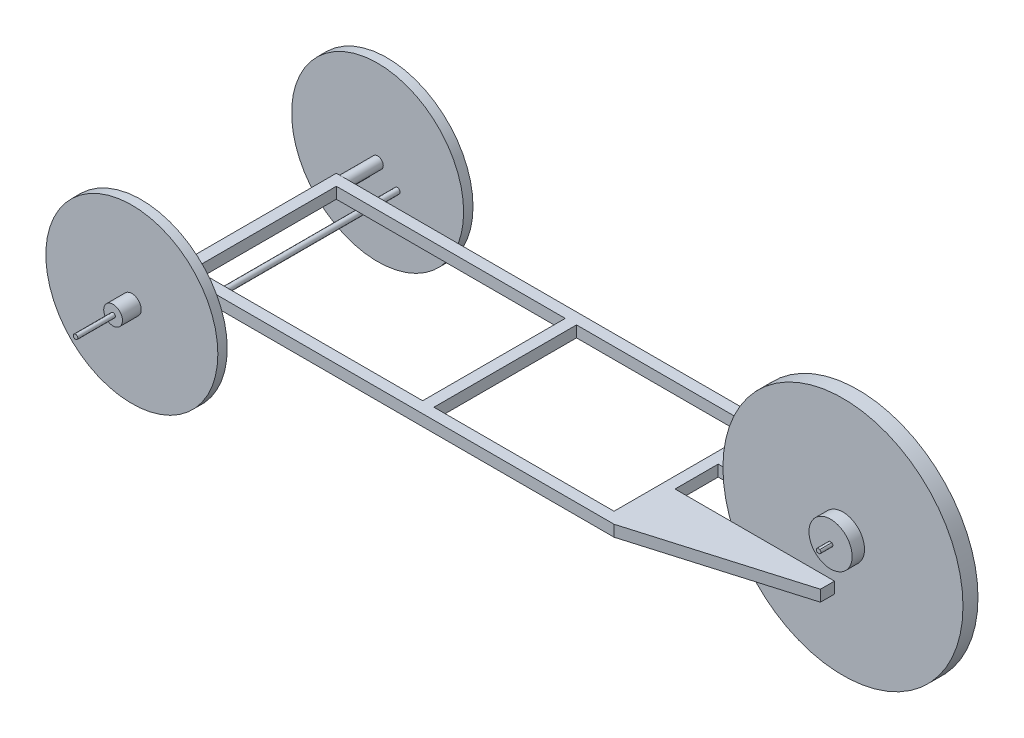
SolidWorks part; units mm, degrees
ref_plane "Front Plane" through (0, 0, 0) normal (0, 0, 1) x (1, 0, 0)
ref_plane "Top Plane" through (0, 0, 0) normal (0, 1, 0) x (1, 0, 0)
ref_plane "Right Plane" through (0, 0, 0) normal (1, 0, 0) x (0, 0, -1)
sketch "Sketch2" plane through (0, 0, 0) normal (0, 1, 0) x (1, 0, 0)
  line L0 (-560, 190) -> (-560, -190)
  line L4 (-560, 190) -> (560, 190)
  line L5 (560, 190) -> (560, -190)
  line L6 (560, -190) -> (-560, -190)
  line L8 (80, 190) -> (80, -190)
  line L9 (50, -190) -> (50, 190)
  line L10 (-560, -190) -> (560, 190) construction
  line L11 (-590, 220) -> (590, 220)
  line L12 (-590, 220) -> (-590, -220)
  line L13 (-590, -220) -> (590, -220)
  line L14 (590, 220) -> (590, -220)
  line L15 (-590, 220) -> (590, -220) construction
  line L16 (-590, 0) -> (-560, 0) construction
  line L17 (50, 0) -> (80, 0) construction
  dimension "D1" = 30
  dimension "D2" = 30
  dimension "D3" = 440
  dimension "D4" = 1180
  dimension "D5" = 540
extrude "Boss-Extrude1" add sketch "Sketch2" along normal blind 15 and the other way blind 15 contours L14 L11 L12 L13 L5 L6 L0 L4 | L9 L6 L8 L4 region at (65, 0, 0) region at (0, 0, -207.4064)
sketch "Sketch3" plane through (0, 0, 0) normal (0, 0, 1) x (1, 0, 0)
  line L0 (-590, -15) -> (590, -15) construction
  line L1 (-590, -15) -> (-590, 15) construction
  line L2 (-590, 15) -> (590, 15) construction
  circle A0 centre (-575, 0) radius 15
extrude "Boss-Extrude2" add sketch "Sketch3" along normal blind 315 and the other way blind 315
sketch "Sketch4" plane through (0, 0, 315) normal (0, 0, 1) x (1, 0, 0)
  circle A0 centre (-575, 0) radius 229.2
  dimension "D1" = 458.4
extrude "Boss-Extrude3" add sketch "Sketch4" along normal blind 25
mirror "Mirror1" about plane through (0, 0, 0) normal (0, 0, 1) of "Boss-Extrude3"
sketch "Sketch5" plane through (0, 0, 0) normal (0, 0, 1) x (1, 0, 0)
  line L0 (1000, 90.7) -> (-590, 0) construction
  line L1 (-590, -15) -> (-590, 0) construction
  line L2 (-575, -229.2) -> (1000, -229.2) construction
  line L3 (-575, 0) -> (-575, -229.2) construction
  circle A0 centre (1000, 90.7) radius 319.9
  circle A1 centre (-575, 0) radius 15 construction
  circle A2 centre (-575, 0) radius 229.2 construction
  dimension "D2" = 639.8
  dimension "D1" = 1590
extrude "Boss-Extrude4" add sketch "Sketch5" along normal blind 20 and the other way blind 20 separate body
sketch "Sketch6" plane through (0, 0, 0) normal (0, 0, 1) x (1, 0, 0)
  circle A0 centre (1000, 90.7) radius 57.5
  dimension "D1" = 115
extrude "Boss-Extrude5" add sketch "Sketch6" along normal blind 53 and the other way blind 43
sketch "Sketch7" plane through (0, 0, 0) normal (0, 0, 1) x (1, 0, 0)
  line L0 (996.6834, 95.7) -> (1003.3166, 95.7)
  line L1 (996.6834, 85.7) -> (1003.3166, 85.7)
  line L2 (1000, 85.7) -> (1000, 95.7) construction
  circle A0 centre (1000, 90.7) radius 6
  dimension "D2" = 12
  dimension "D1" = 10
extrude "Boss-Extrude6" add sketch "Sketch7" along normal blind 85 and the other way blind 75 contours L2 L1 A0 L0 | L1 L2 L0 A0 region at (997.3422, 90.7, 0) region at (1002.6578, 90.7, 0)
sketch "Sketch8" plane through (0, 0, 0) normal (0, 1, 0) x (1, 0, 0)
  line L0 (590, -220) -> (1015, -95)
  line L1 (1015, -95) -> (1015, 95)
  line L2 (1015, 95) -> (590, 220)
  line L3 (590, 220) -> (590, 57.5)
  line L4 (590, 220) -> (590, -220) construction
  line L5 (590, 57.5) -> (985, 57.5)
  line L6 (985, 57.5) -> (985, -57.5)
  line L7 (985, -57.5) -> (590, -57.5)
  line L8 (590, -57.5) -> (590, -220)
  line L9 (985, -57.5) -> (1015, -57.5)
  line L10 (985, 57.5) -> (1015, 57.5)
  line L11 (985, 0) -> (590, 0) construction
  line L12 (1000, 75) -> (1000, 0) construction
  line L13 (996.6834, 75) -> (1003.3166, 75) construction
  line L14 (985, 0) -> (1015, 0) construction
  dimension "D1" = 30
  dimension "D2" = 115
  dimension "D3" = 95
extrude "Boss-Extrude7" add sketch "Sketch8" against normal up to surface (15 mm away) and the other way up to surface (15 mm away) contours L9 L7 L8 L0 L1 | L5 L10 L1 L2 L3 region at (758.2292, 0, 114.0104) region at (758.2292, 0, -114.0104) up to face at (-191.6667, -15, 0) other way up to face at (-191.6667, 15, 0)
sketch "Sketch9" plane through (0, 0, 0) normal (0, 1, 0) x (1, 0, 0)
  line L0 (-575, 655.2435) -> (-575, -495.4754) construction
  line L1 (-560, 0) -> (-590, 0) construction
  line L2 (-560, 190) -> (-560, -190) construction
  line L3 (-590, 220) -> (-590, -220) construction
  line L4 (-560, 220) -> (-560, 320)
  line L5 (-575, 220) -> (590, 220) construction
  line L6 (-560, 320) -> (-550, 320)
  line L7 (-550, 320) -> (-550, 390)
  line L8 (-550, 390) -> (-569, 390)
  line L9 (-569, 390) -> (-569, 490)
  line L10 (-569, 490) -> (-575, 490)
  line L11 (-575, 490) -> (-575, 220)
  line L12 (-575, 220) -> (-560, 220)
  line L13 (-575, -220) -> (-560, -220)
  line L14 (-575, -490) -> (-575, -220)
  line L15 (-569, -490) -> (-575, -490)
  line L16 (-569, -390) -> (-569, -490)
  line L17 (-550, -390) -> (-569, -390)
  line L18 (-550, -320) -> (-550, -390)
  line L19 (-560, -320) -> (-550, -320)
  line L20 (-560, -220) -> (-560, -320)
  point P8 (-575, 0)
  point P17 (-555, 320)
  dimension "D1" = 15
  dimension "D2" = 6
  dimension "D3" = 25
  dimension "D4" = 100
  dimension "D5" = 170
  dimension "D6" = 100
revolve "Revolve1" add sketch "Sketch9" angle 360 about L0
sketch "Sketch10" plane through (0, 0, 0) normal (0, 0, 1) x (1, 0, 0)
  line L0 (-602.5, -39) -> (-595, -39) construction
  line L1 (-595, -39) -> (-590, -15) construction
  line L2 (-560, -15) -> (-530, -39) construction
  line L3 (-530, -39) -> (-522.5, -39) construction
  line L4 (-595, -39) -> (-530, -39) construction
  circle A0 centre (-602.5, -39) radius 7.5
  circle A1 centre (-522.5, -39) radius 7.5
  dimension "D1" = 15
  dimension "D2" = 5
  dimension "D3" = 30
  dimension "D4" = 24
extrude "Boss-Extrude8" add sketch "Sketch10" along normal up to surface and the other way up to surface up to face at (-560, 0, 315) other way up to face at (-560, 0, -315)
